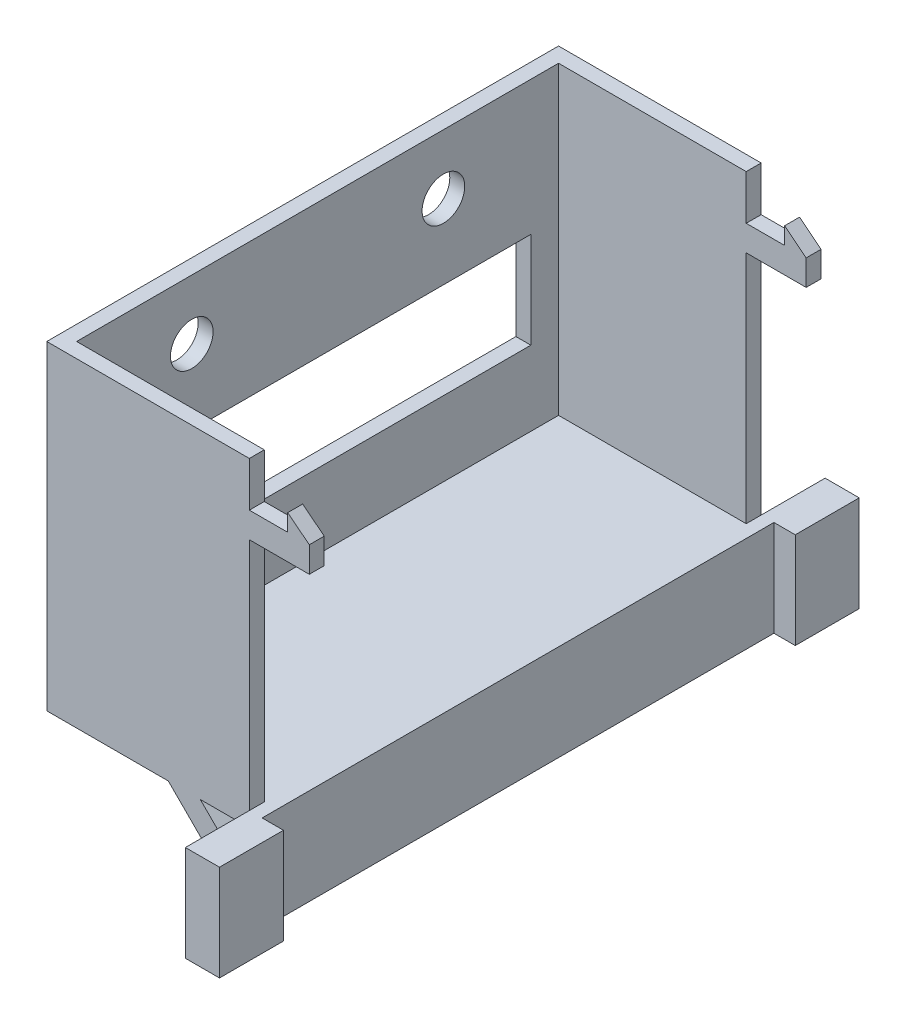
SolidWorks part; units mm, degrees
ref_plane "Front Plane" through (0, 0, 0) normal (0, 0, 1) x (1, 0, 0)
ref_plane "Top Plane" through (0, 0, 0) normal (0, 1, 0) x (1, 0, 0)
ref_plane "Right Plane" through (0, 0, 0) normal (1, 0, 0) x (0, 0, -1)
sketch "Sketch1" plane through (0, 0, 0) normal (1, 0, 0) x (0, 0, -1)
  line L0 (0, 0) -> (0, -11.43)
  line L1 (0, 0) -> (76.2, 0)
  line L5 (0, -11.43) -> (76.2, -11.43)
  line L6 (76.2, -11.43) -> (76.2, 0)
  line L7 (7.62, 0) -> (7.62, -11.43)
  line L8 (68.58, 0) -> (68.58, -11.43)
  line L9 (7.62, -1.778) -> (68.58, -1.778)
  dimension "D1" = 7.62
  dimension "D2" = 7.62
  dimension "D3" = 76.2
  dimension "D4" = 11.43
  dimension "D5" = 1.778
extrude "Boss-Extrude1" add sketch "Sketch1" along normal blind 4.064 contours L7 L1 L0 L5 | L1 L8 L5 L6 region at (0, -5.715, -3.81) region at (0, -5.715, -72.39)
extrude "Boss-Extrude2" add sketch "Sketch1<3>" along normal blind 1.524 contours L9 L7 L5 L8 | L7 L9 L8 L1 region at (0, -0.889, -38.1) region at (0, -6.604, -38.1)
sketch "Sketch1<3>" plane through (0, 0, 0) normal (1, 0, 0) x (0, 0, -1) same geometry as "Sketch1"
extrude "Boss-Extrude3" add sketch "Sketch1<6>" against normal blind 24.13 contours L7 L9 L8 L1 region at (0, -0.889, -38.1)
sketch "Sketch1<6>" plane through (0, 0, 0) normal (1, 0, 0) x (0, 0, -1) same geometry as "Sketch1"
sketch "Sketch4" plane through (0, -1.778, 0) normal (0, -1, 0) x (1, 0, 0)
  line L0 (0, -7.62) -> (-24.13, -7.62)
  line L1 (-24.13, -7.62) -> (-24.13, -68.58)
  line L2 (-24.13, -68.58) -> (0, -68.58)
  line L3 (-22.352, -66.802) -> (0, -66.802)
  line L4 (0, -66.802) -> (0, -68.58)
  line L5 (-22.352, -66.802) -> (-22.352, -9.398)
  line L6 (-22.352, -9.398) -> (0, -9.398)
  line L7 (0, -7.62) -> (0, -68.58) construction
  line L8 (0, -9.398) -> (0, -7.62)
  dimension "D1" = 1.778
  dimension "D2" = 1.778
  dimension "D3" = 1.778
extrude "Boss-Extrude4" add sketch "Sketch4" against normal blind 38.1
sketch "Sketch5" plane through (0, 0, -68.58) normal (0, 0, -1) x (-1, 0, 0)
  line L0 (0, -1.778) -> (1.778, -1.778)
  line L1 (24.13, -1.778) -> (0, -1.778) construction
  line L2 (1.778, -1.778) -> (0, -3.556)
  line L3 (0, -3.556) -> (0, -1.778)
  line L8 (5.842, -1.778) -> (9.652, -1.778)
  line L9 (9.652, -1.778) -> (0, -11.43)
  line L10 (0, -11.43) -> (0, -7.62)
  line L11 (5.842, -1.778) -> (0, -7.62)
  line L12 (24.13, -1.778) -> (0, -1.778) construction
  line M2 (0, -1.778) -> (24.13, -1.778)
extrude "Boss-Extrude7" add sketch "Sketch5<4>" against normal up to surface (60.96 mm away) contours L3 L2 M2 region at (-0.5927, -2.3707, -68.58) up to face at (-9.652, 17.6276, -7.62)
sketch "Sketch5<4>" plane through (0, 0, -68.58) normal (0, 0, -1) x (-1, 0, 0) same geometry as "Sketch5"
extrude "Boss-Extrude8" add sketch "Sketch5<5>" against normal up to surface (60.96 mm away) contours L11 L10 L9 M2 region at (-3.9516, -5.7296, -68.58) up to face at (-8.3397, 14.2452, -7.62)
sketch "Sketch5<5>" plane through (0, 0, -68.58) normal (0, 0, -1) x (-1, 0, 0) same geometry as "Sketch5"
extrude "Cut-Extrude2" cut sketch "Sketch5" against normal blind 50.8 from offset 5.08 contours L11 L10 L9 M2 region at (-3.9516, -5.7296, -68.58) offset against normal yes
sketch "Sketch6" plane through (-22.352, 0, 0) normal (1, 0, 0) x (0, 0, -1)
  line L0 (9.398, 36.322) -> (9.398, 0) construction
  line L1 (9.398, 0) -> (66.802, 0) construction
  line L2 (66.802, 0) -> (66.802, 36.322) construction
  line L3 (66.802, 36.322) -> (9.398, 36.322) construction
  line L4 (38.1, 36.322) -> (38.1, 0) construction
  line L5 (38.1, 29.21) -> (23.114, 29.21) construction
  line L6 (38.1, 29.21) -> (53.086, 29.21) construction
  line L7 (38.1, 20.32) -> (12.7, 20.32)
  line L8 (12.7, 20.32) -> (12.7, 8.89)
  line L9 (12.7, 8.89) -> (63.5, 8.89)
  line L10 (63.5, 8.89) -> (63.5, 20.32)
  line L11 (63.5, 20.32) -> (38.1, 20.32)
  circle A0 centre (23.114, 29.21) radius 2.54
  circle A1 centre (53.086, 29.21) radius 2.54
  dimension "D1" = 8.89
  dimension "D2" = 8.89
  dimension "D3" = 20.32
extrude "Cut-Extrude3" cut sketch "Sketch6" against normal through all
extrude "Boss-Extrude9" add sketch "Sketch5<12>" against normal blind 5.08 from offset 27.94 contours L11 L10 L9 M2 region at (-3.9516, -5.7296, -68.58) offset against normal yes
sketch "Sketch5<12>" plane through (0, 0, -68.58) normal (0, 0, -1) x (-1, 0, 0) same geometry as "Sketch5"
sketch "Sketch9" plane through (0, 0, -7.62) normal (0, 0, 1) x (1, 0, 0)
  line L0 (0, 27.94) -> (0, 30.988)
  line L1 (0, 36.322) -> (0, 0) construction
  line L2 (0, 0) -> (0, 27.94) construction
  line L3 (0, 30.988) -> (4.572, 30.988)
  line L4 (4.572, 30.988) -> (4.572, 33.02)
  line L5 (4.572, 33.02) -> (7.1403, 30.988)
  line L6 (7.1403, 30.988) -> (7.1403, 27.94)
  line L7 (7.1403, 27.94) -> (0, 27.94)
  dimension "D1" = 3.048
  dimension "D2" = 2.032
  dimension "D3" = 4.572
extrude "Boss-Extrude10" add sketch "Sketch9" against normal up to surface (60.96 mm away) up to face at (-6.5532, 6.2865, -68.58)
extrude "Cut-Extrude4" cut sketch "Sketch9<2>" against normal blind 57.404 from offset 1.778 offset against normal yes
sketch "Sketch9<2>" plane through (0, 0, -7.62) normal (0, 0, 1) x (1, 0, 0) same geometry as "Sketch9"
sketch "Sketch10" plane through (0, 0, -68.58) normal (0, 0, -1) x (-1, 0, 0)
  line L0 (0, 36.322) -> (24.13, 36.322) construction
  line L1 (24.13, 36.322) -> (24.13, -1.778) construction
  line L2 (24.13, -1.778) -> (0, -1.778) construction
  line L3 (0, -1.778) -> (0, 36.322) construction
  line L5 (2.54, 32.512) -> (19.05, 32.512)
  line L6 (2.54, 32.512) -> (2.54, 30.734)
  line L7 (2.54, 30.734) -> (19.05, 30.734)
  line L8 (19.05, 32.512) -> (19.05, 30.734)
  line L13 (2.54, 24.384) -> (19.05, 24.384)
  line L14 (2.54, 24.384) -> (2.54, 22.606)
  line L15 (2.54, 22.606) -> (19.05, 22.606)
  line L16 (19.05, 24.384) -> (19.05, 22.606)
  line L21 (2.54, 16.256) -> (19.05, 16.256)
  line L22 (2.54, 16.256) -> (2.54, 14.478)
  line L23 (2.54, 14.478) -> (19.05, 14.478)
  line L24 (19.05, 16.256) -> (19.05, 14.478)
  line L29 (2.54, 8.128) -> (19.05, 8.128)
  line L30 (2.54, 8.128) -> (2.54, 6.35)
  line L31 (2.54, 6.35) -> (19.05, 6.35)
  line L32 (19.05, 8.128) -> (19.05, 6.35)
  dimension "D1" = 3.81
  dimension "D2" = 6.35
  dimension "D3" = 6.35
  dimension "D4" = 6.35
  dimension "D5" = 2.54
